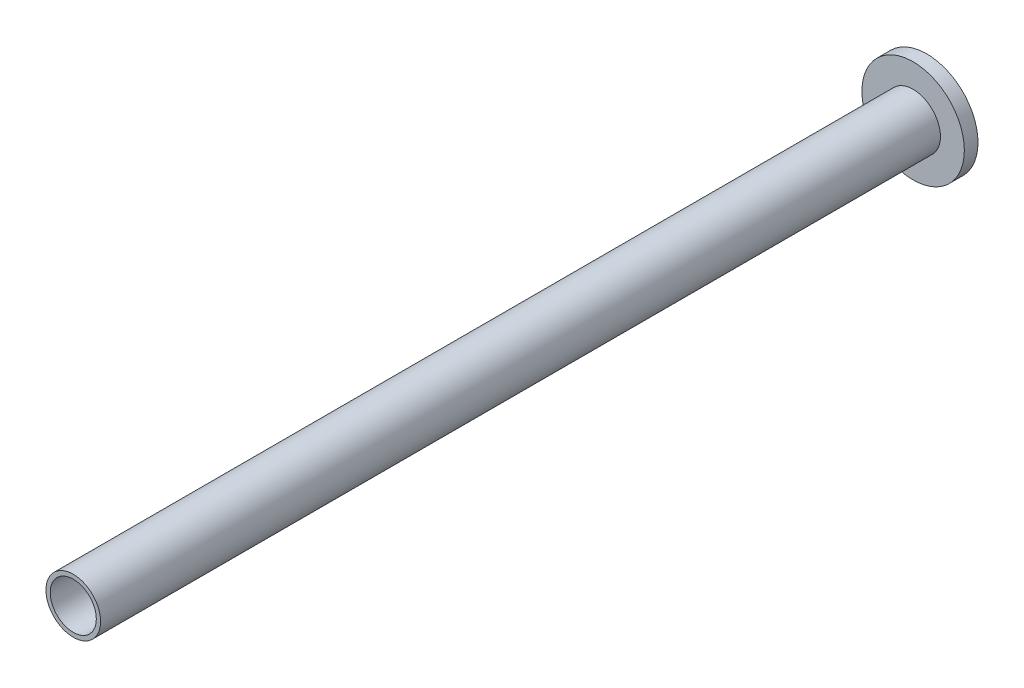
SolidWorks part; units mm, degrees
material "6061-T6 (SS)"
ref_plane "Front Plane" through (0, 0, 0) normal (0, 0, 1) x (1, 0, 0)
ref_plane "Top Plane" through (0, 0, 0) normal (0, 1, 0) x (1, 0, 0)
ref_plane "Right Plane" through (0, 0, 0) normal (1, 0, 0) x (0, 0, -1)
sketch "Extrude sketch 1" plane through (0, 0, 0) normal (0, 0, 1) x (1, 0, 0)
  circle A0 centre (860, 225) radius 30
  dimension "D1" = 60
extrude "Extrude 1" add sketch "Extrude sketch 1" along normal blind 8 from offset 300 separate body
sketch "Extrude sketch 2" plane through (0, 0, 0) normal (0, 0, 1) x (1, 0, 0)
  circle A0 centre (860, 225) radius 16
  circle A1 centre (860, 225) radius 13.5
  dimension "D1" = 27
  dimension "D2" = 32
extrude "Extrude 2" add sketch "Extrude sketch 2" along normal blind 492 from offset 308 separate body
combine bodies "Combine (weld / assembly of features)" operation type add bodies to combine 101 102
